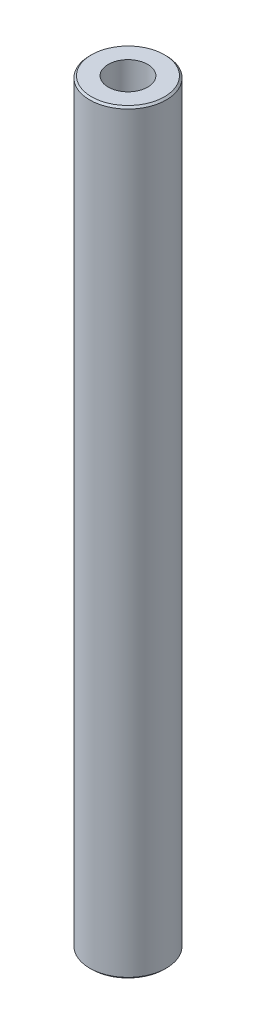
SolidWorks part; units mm, degrees
ref_plane "Front Plane" through (0, 0, 0) normal (0, 0, 1) x (1, 0, 0)
ref_plane "Top Plane" through (0, 0, 0) normal (0, 1, 0) x (1, 0, 0)
ref_plane "Right Plane" through (0, 0, 0) normal (1, 0, 0) x (0, 0, -1)
sketch "Sketch1" plane through (0, 0, 0) normal (0, 1, 0) x (1, 0, 0)
  circle A0 centre (0, 0) radius 7.5
  dimension "SHAFT_OD" = 15
extrude "Boss-Extrude1" add sketch "Sketch1" along normal blind 148.0998
sketch "Sketch2" plane through (0, 0, 0) normal (0, 1, 0) x (1, 0, 0)
  circle A0 centre (0, 0) radius 3.8721
  dimension "BORE_D" = 7.7442
extrude "Cut-Extrude1" cut sketch "Sketch2" along normal through all
chamfer "Chamfer1" distance 0.3575 angle 45 2 edges at (0, 148.0998, 7.5) (0, 0, 7.5)
